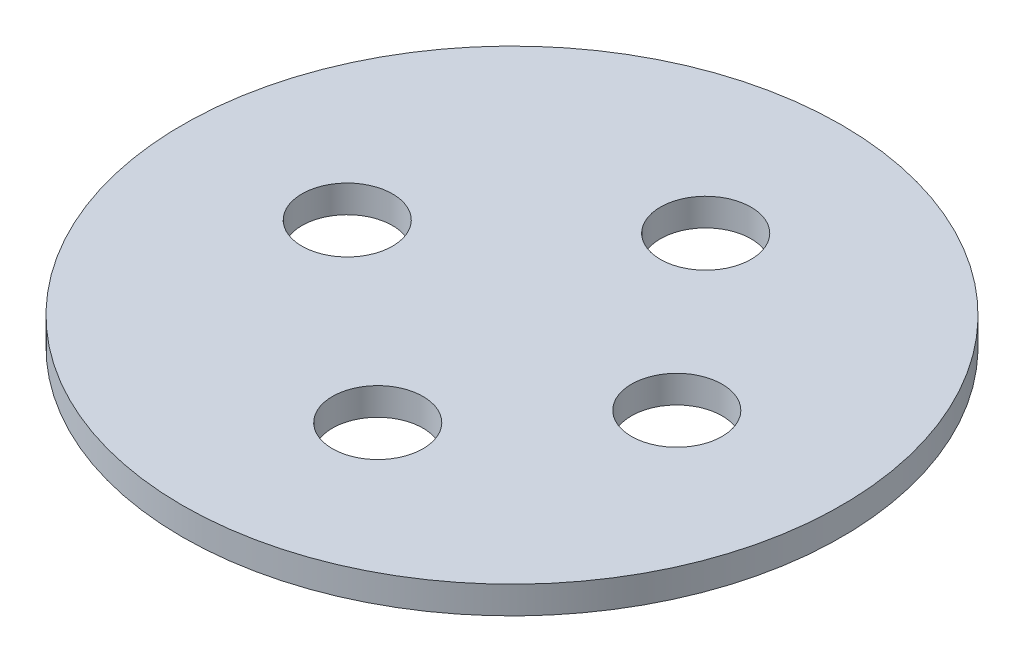
SolidWorks part; units mm, degrees
ref_plane "Front Plane" through (0, 0, 0) normal (0, 0, 1) x (1, 0, 0)
ref_plane "Top Plane" through (0, 0, 0) normal (0, 1, 0) x (1, 0, 0)
ref_plane "Right Plane" through (0, 0, 0) normal (1, 0, 0) x (0, 0, -1)
sketch "Sketch1" plane through (0, 0, 0) normal (0, 1, 0) x (1, 0, 0)
  line L0 (-3.3452, 0.9469) -> (-3.3452, 6.6208) construction
  line L1 (-3.3452, 6.6208) -> (-3.3452, -5.5783) construction
  line L2 (-3.3452, 0.9469) -> (17.6697, 0.9469) construction
  line L3 (-3.3452, 0.9469) -> (-17.6697, 0.9469) construction
  line L4 (-1.3452, 0.9469) -> (-1.3452, 13.0844) construction
  line L5 (-1.3452, 13.0844) -> (-1.3452, -12.3317) construction
  line L6 (0.6548, 0.9469) -> (0.6548, 13.4396) construction
  line L7 (0.6548, 13.4396) -> (0.6548, -12.6475) construction
  line L8 (-0.4023, 13.0844) -> (-0.4023, -11.4659) construction
  circle A2 centre (-0.4023, 7.0564) radius 1.65
  circle A4 centre (-0.4023, -4.8856) radius 1.65
  circle A8 centre (-1.3452, 0.9469) radius 12
  circle A10 centre (-7.3452, 0.9469) radius 1.65
  circle A11 centre (4.6548, 0.9469) radius 1.65
  dimension "D5" = 3.3
  dimension "D7" = 3.3
  dimension "D11" = 24
  dimension "D13" = 3.3
  dimension "D14" = 3.3
  dimension "D2" = 2
  dimension "D3" = 2
  dimension "D15" = 6
  dimension "D16" = 6
extrude "Boss-Extrude1" add sketch "Sketch1" against normal blind 1 contours A8
extrude "Cut-Extrude1" cut sketch "Sketch1<3>" against normal blind 1 contours A10 | A2 | A4 | A11
sketch "Sketch1<3>" plane through (0, 0, 0) normal (0, 1, 0) x (1, 0, 0) same geometry as "Sketch1"
equation "\"R\"= 63mm"
equation "\"E\"= 2mm"
equation "\"Rr\"= 5"
equation "\"N\"= 22"
equation "\"M5\"= 5"
equation "\"SMALL_BEARING_DEPTH\"= 6MM"
